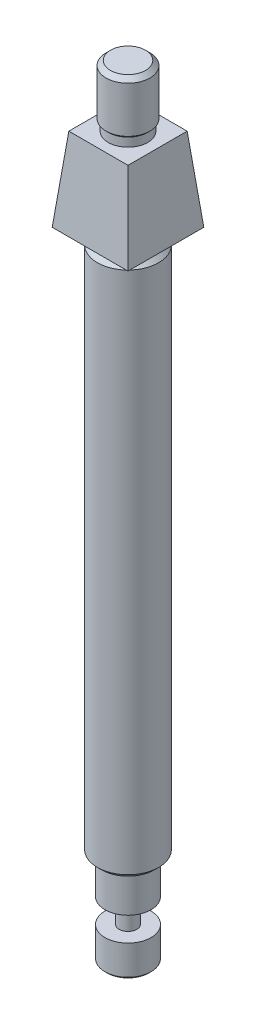
SolidWorks part; units mm, degrees
material "1.0050 (E295)"
ref_plane "Front Plane" through (0, 0, 0) normal (0, 0, 1) x (1, 0, 0)
ref_plane "Top Plane" through (0, 0, 0) normal (0, 1, 0) x (1, 0, 0)
ref_plane "Right Plane" through (0, 0, 0) normal (1, 0, 0) x (0, 0, -1)
sketch "Sketch1" plane through (0, 0, 0) normal (0, 1, 0) x (1, 0, 0)
  circle A0 centre (0, 0) radius 10.5
  dimension "D1" = 21
extrude "Boss-Extrude1" add sketch "Sketch1" along normal blind 42
sketch "Sketch3" plane through (0, 42, 0) normal (0, 1, 0) x (1, 0, 0)
  circle A0 centre (0, 0) radius 14
  dimension "D1" = 28
extrude "Boss-Extrude2" add sketch "Sketch3" along normal blind 243
sketch "Sketch4" plane through (0, 285, 0) normal (0, 1, 0) x (1, 0, 0)
  circle A0 centre (0, 0) radius 9
  dimension "D1" = 18
extrude "Boss-Extrude3" add sketch "Sketch4" along normal blind 5
sketch "Sketch5" plane through (0, 290, 0) normal (0, 1, 0) x (1, 0, 0)
  line L1 (-17.3, -17.3) -> (17.3, -17.3)
  line L2 (-17.3, -17.3) -> (-17.3, 17.3)
  line L3 (-17.3, 17.3) -> (17.3, 17.3)
  line L4 (17.3, -17.3) -> (17.3, 17.3)
  line L5 (-17.3, -17.3) -> (17.3, 17.3) construction
  line L6 (-17.3, 17.3) -> (17.3, -17.3) construction
  point P0 (0, 0)
  dimension "D1" = 34.6
  dimension "D2" = 34.6
extrude "Boss-Extrude4" add sketch "Sketch5" along normal blind 38 draft 5.711
sketch "Sketch6" plane through (0, 328, 0) normal (0, 1, 0) x (1, 0, 0)
  circle A0 centre (0, 0) radius 9
  dimension "D1" = 18
extrude "Boss-Extrude6" add sketch "Sketch6" along normal blind 3 contours A0
sketch "Sketch7" plane through (0, 331, 0) normal (0, 1, 0) x (1, 0, 0)
  circle A0 centre (0, 0) radius 10
  dimension "D1" = 20
extrude "Boss-Extrude7" add sketch "Sketch7" along normal blind 25
chamfer "Chamfer1" distance 2 angle 45 2 edges at (0, 331, 10) (0, 356, 10)
fillet "Fillet2" radius 2.5 2 edges at (0, 285, 9) (0, 290, 9)
sketch "Sketch8" plane through (0, 0, 0) normal (0, 0, 1) x (1, 0, 0)
  line L0 (-10.5, 42) -> (-10.5, 0) construction
  line L1 (-10.5, 25.5) -> (-4, 25.5)
  line L2 (-10.5, 25.5) -> (-10.5, 14.5)
  line L3 (-10.5, 14.5) -> (-4, 14.5)
  line L4 (-4, 25.5) -> (-4, 14.5)
  line L5 (-14, 42) -> (14, 42) construction
  point P6 (-10.5, 20)
  dimension "D1" = 11
  dimension "D2" = 4
  dimension "D3" = 22
revolve "Cut-Revolve1" cut sketch "Sketch8" angle 360 about axis through (0, 42, 0) along (0, -1, 0)
chamfer "Chamfer2" distance 2 angle 45 2 edges at (0, 42, 14) (0, 285, 14)
chamfer "Chamfer3" distance 1 angle 45 1 edges at (0, 0, 10.5)
equation "\"D3@Boss-Extrude4\"=atn(0.1)"
